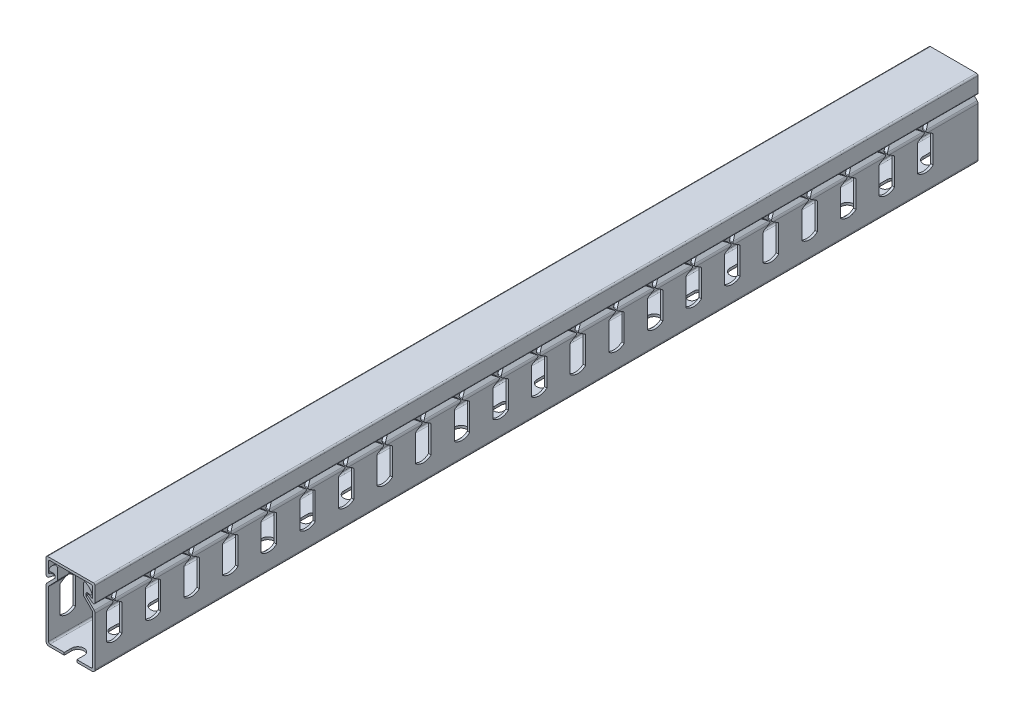
SolidWorks part; units mm, degrees
ref_plane "Front Plane" through (0, 0, 0) normal (0, 0, 1) x (1, 0, 0)
ref_plane "Top Plane" through (0, 0, 0) normal (0, 1, 0) x (1, 0, 0)
ref_plane "Right Plane" through (0, 0, 0) normal (1, 0, 0) x (0, 0, -1)
sketch "Sketch1" plane through (0, 0, 0) normal (0, 0, 1) x (1, 0, 0)
  line L0 (-12.7, 10.6985) -> (12.7, 10.6985) construction
  line L1 (12.7, -20) -> (-12.7, -20) construction
  line L2 (12.7, -20) -> (12.7, 20) construction
  line L3 (12.7, 20) -> (-12.7, 20) construction
  line L4 (-12.7, -20) -> (-12.7, 20) construction
  line L5 (0, 20) -> (0, -20) construction
  line L6 (12.7, 0) -> (-12.7, 0) construction
  line L7 (-12.7, 13.7872) -> (12.7, 13.7872) construction
  line L8 (6.8085, 20) -> (6.8085, 10.6985) construction
  line L9 (-6.8085, 20) -> (6.8085, 10.6985) construction
  line L10 (-6.8085, 20) -> (-6.8085, 10.6985) construction
  line L11 (-12.7, 18.222) -> (12.7, 18.222) construction
  line L12 (-12.7, 13.6284) -> (12.7, 13.6284) construction
  line L13 (-11.4341, 10.8542) -> (-7.685, 13.6284) construction
  line L14 (-10.1877, 13.798) -> (-6.8085, 14.3635) construction
  line L15 (12.7, 7.4) -> (6.8085, 13.4162) construction
  circle A0 centre (-11.9062, 11.4923) radius 0.7938 construction
  circle A1 centre (-10.3187, 14.5809) radius 0.7937 construction
  circle A2 centre (-7.6022, 17.4283) radius 0.7938 construction
  arc A3 (-7.9835, 18.1244) -> (-11.0321, 14.929) centre (-4.4831, 11.7329) ccw construction
  point P0 (0, 0)
  point P4 (11.43, 0)
  point P13 (0, 15.3493)
  point P16 (-11.1125, 13.7872)
  point P21 (-11.1125, 11.4923)
  point P26 (-10.3188, 13.7872)
  point P27 (-10.3188, 13.7872)
  point P28 (-11.1125, 14.5809)
  point P36 (12.7, 7.4)
  dimension "D6" = 7.2873
  dimension "Width" = 25.4
  dimension "Heigth" = 40
  dimension "Wall Thickness" = 1.27
  dimension "Cap Height" = 9.3015
  dimension "Lip Height" = 6.2128
  dimension "D1" = 13.6169
  dimension "D2" = 1.778
  dimension "Lip From Edge" = 1.5875
  dimension "D4" = 0.1588
  dimension "D5" = 36.5
  dimension "D3" = 80.5
  dimension "Shoulder Height" = 27.4
  dimension "D7" = 44.4
sketch "Sketch3" plane through (0, 0, 0) normal (1, 0, 0) x (0, 0, -1)
  line L0 (228.6, 0) -> (-228.6, 0) construction
  line L1 (-228.6, 20) -> (-228.6, -20) construction
  line L2 (-228.6, -20) -> (228.6, -20) construction
  line L3 (228.6, -20) -> (228.6, 20) construction
  line L4 (228.6, 20) -> (-228.6, 20) construction
  line L5 (-214.6, 20) -> (-214.6, 9.8437) construction
  line L6 (-214.6, 9.8437) -> (-218.473, 7.4) construction
  line L7 (-218.473, 7.4) -> (-218.727, 7.4) construction
  line L8 (-218.727, 7.4) -> (-222.6, 9.8437) construction
  line L9 (-222.6, 9.8437) -> (-222.6, 20) construction
  line L10 (-218.727, 7.4) -> (-222.6, 4.9563) construction
  line L11 (-222.6, 4.9563) -> (-222.6, -9.1796) construction
  line L12 (-222.6, -9.1796) -> (-214.6, -9.1796) construction
  line L13 (-214.6, -9.1796) -> (-214.6, 4.9563) construction
  line L14 (-218.473, 7.4) -> (-214.6, 4.9563) construction
  line L15 (-218.6, 7.4) -> (-218.6, -9.1796) construction
  line L16 (-218.6, 7.4) -> (-218.6, 20) construction
  line L17 (-222.6, 4.9563) -> (-214.6, 4.9563) construction
  line L18 (0, 7.4) -> (-218.473, 7.4) construction
  line L19 (-222.6, 9.8437) -> (-222.6, 4.9563) construction
  line L20 (-218.727, 7.4) -> (-222.6, 7.4) construction
  line L21 (-214.6, 4.9563) -> (-202.6, 4.9563) construction
  line L22 (-202.6, 4.9563) -> (-194.6, 4.9563) construction
  line L23 (-198.6, 4.9563) -> (-198.6, -9.1796) construction
  line L24 (-101.6, 20) -> (-101.6, -20) construction
  line L25 (101.6, 20) -> (101.6, -20) construction
  arc A0 (-222.6, -9.1796) -> (-214.6, -9.1796) centre (-218.6, -4.7075) ccw construction
  circle A1 centre (-219.4707, 7.4) radius 0.3969 construction
  circle A2 centre (-217.7293, 7.4) radius 0.3969 construction
  point P29 (-194.6, 4.9563)
  point P30 (-202.6, 4.9563)
  point P31 (-202.6, 4.9563)
  point P32 (-198.6, 4.9563)
  point P34 (-101.6, 0)
  point P39 (101.6, 0)
  dimension "D2" = 6
  dimension "D6" = 0.7937
  dimension "Length" = 457.2
  dimension "Side Cut Out Width" = 8
  dimension "D3" = 6
  dimension "D1" = 10.8204
  dimension "D4" = 64.5
  dimension "D5" = 0.254
  dimension "Cut Spacing" = 12
  dimension "Cut Center To Center" = 20
  dimension "D7" = 127
  dimension "D8" = 127
sketch "Sketch4" plane through (0, 0, 0) normal (0, 1, 0) x (1, 0, 0)
  line L0 (0, -232.35) -> (0, -224.85) construction
  line L1 (-12.7, 228.6) -> (12.7, 228.6) construction
  line L2 (-12.7, 228.6) -> (-12.7, -228.6) construction
  line L3 (-12.7, -228.6) -> (12.7, -228.6) construction
  line L4 (12.7, 228.6) -> (12.7, -228.6) construction
  line L5 (0, -228.6) -> (0, 228.6) construction
  line L6 (-12.7, 0) -> (12.7, 0) construction
  line L7 (-3.25, -232.35) -> (-3.25, -224.85) construction
  line L8 (3.25, -232.35) -> (3.25, -224.85) construction
  line L9 (0, -206.1) -> (0, -202.6) construction
  line L10 (-2.25, -206.1) -> (-2.25, -202.6) construction
  line L11 (2.25, -206.1) -> (2.25, -202.6) construction
  line L12 (0, -183.85) -> (0, -176.35) construction
  line L13 (-3.25, -183.85) -> (-3.25, -176.35) construction
  line L14 (3.25, -183.85) -> (3.25, -176.35) construction
  line L15 (0, -153.35) -> (0, -156.85) construction
  line L16 (2.25, -153.35) -> (2.25, -156.85) construction
  line L17 (-2.25, -153.35) -> (-2.25, -156.85) construction
  line L18 (-12.7, -101.6) -> (12.7, -101.6) construction
  line L19 (-12.7, 101.6) -> (12.7, 101.6) construction
  arc A0 (-3.25, -232.35) -> (3.25, -232.35) centre (0, -232.35) ccw construction
  arc A1 (3.25, -224.85) -> (-3.25, -224.85) centre (0, -224.85) ccw construction
  arc A2 (-2.25, -206.1) -> (2.25, -206.1) centre (0, -206.1) ccw construction
  arc A3 (2.25, -202.6) -> (-2.25, -202.6) centre (0, -202.6) ccw construction
  arc A4 (-3.25, -183.85) -> (3.25, -183.85) centre (0, -183.85) ccw construction
  arc A5 (3.25, -176.35) -> (-3.25, -176.35) centre (0, -176.35) ccw construction
  arc A6 (2.25, -153.35) -> (-2.25, -153.35) centre (0, -153.35) ccw construction
  arc A7 (-2.25, -156.85) -> (2.25, -156.85) centre (0, -156.85) ccw construction
  point P0 (0, 0)
  point P5 (0, -228.6)
  point P13 (0, -204.35)
  point P18 (0, -200.35)
  point P19 (0, -208.35)
  point P20 (0, -221.6)
  point P21 (0, -235.6)
  point P24 (0, -180.1)
  point P31 (0, -155.1)
  point P40 (0, -187.1)
  point P41 (0, -173.1)
  dimension "Large Hole Radius" = 3.25
  dimension "Large Hole Length" = 14
  dimension "Slot With" = 8
  dimension "End Hole Spacing" = 48.5
  dimension "D4" = 24.25
  dimension "Hole Spacing" = 25
  dimension "Mounting Hole Diameter" = 4.5
sketch "Sketch5" plane through (0, 0, 0) normal (0, 0, 1) x (1, 0, 0)
  line L0 (-6.8085, 17.4283) -> (-6.8085, 11.6011)
  line L1 (-6.8085, 20) -> (-6.8085, 10.6985) construction
  line L2 (-6.8085, 11.6011) -> (-11.43, 6.8817)
  line L3 (-11.43, 6.8817) -> (-11.43, -18.73)
  line L4 (-11.43, -18.73) -> (11.43, -18.73)
  line L5 (11.43, -18.73) -> (11.43, 6.8817)
  line L6 (11.43, 6.8817) -> (6.8085, 11.6011)
  line L7 (6.8085, 11.6011) -> (6.8085, 17.4283)
  line L8 (6.8085, 20) -> (6.8085, 10.6985) construction
  line L9 (12.7, 7.4) -> (6.8085, 13.4162) construction
  line L10 (0, 20) -> (0, -20) construction
  line L11 (11.43, 0) -> (12.7, 0) construction
  line L12 (8.0785, 12.1194) -> (6.8085, 12.1194) construction
  line L13 (-10.1877, 13.798) -> (-6.8085, 14.3635) construction
  line L14 (-10.1877, 13.798) -> (-8.0785, 14.151)
  line L15 (-8.0785, 14.151) -> (-8.0785, 12.1194)
  line L16 (-8.0785, 12.1194) -> (-12.7, 7.4)
  line L17 (-12.7, -20) -> (-12.7, 20) construction
  line L18 (-12.7, 7.4) -> (-12.7, -20)
  line L19 (-12.7, -20) -> (12.7, -20)
  line L20 (12.7, -20) -> (12.7, 7.4)
  line L21 (12.7, 7.4) -> (8.0785, 12.1194)
  line L22 (8.0785, 12.1194) -> (8.0785, 14.151)
  line L23 (6.8085, 12.1194) -> (-6.8085, 12.1194) construction
  line L24 (-6.8085, 12.1194) -> (-8.0785, 12.1194) construction
  line L25 (11.43, 6.8817) -> (12.3374, 7.7703) construction
  line L26 (-12.7, 18.222) -> (12.7, 18.222) construction
  line L27 (10.1877, 13.798) -> (8.0785, 14.151)
  line L28 (11.43, -18.73) -> (11.43, -20) construction
  line L29 (-12.7, 20) -> (-12.7, 11.4923)
  line L30 (-12.7, 20) -> (12.7, 20)
  line L31 (-11.4341, 10.8542) -> (-8.7512, 12.8395)
  line L32 (-11.4341, 10.8542) -> (-7.685, 13.6284) construction
  line L33 (12.7, 20) -> (12.7, 11.4923)
  line L34 (12.7, -20) -> (12.7, 20) construction
  line L35 (8.7512, 12.8395) -> (11.4341, 10.8542)
  line L36 (-12.7, 10.6985) -> (12.7, 10.6985) construction
  line L37 (-11.43, 12.4371) -> (-11.43, 18.73)
  line L38 (-11.43, 18.73) -> (11.43, 18.73)
  line L39 (11.43, 18.73) -> (11.43, 12.4371)
  line L40 (-11.43, 18.73) -> (-11.43, 20) construction
  line L41 (-11.43, 18.73) -> (-12.7, 18.73) construction
  line L42 (-11.43, 12.4371) -> (-10.6707, 12.999)
  line L43 (-11.0503, 12.7181) -> (-10.2949, 11.6972) construction
  line L44 (-8.9869, 13.5542) -> (-8.9869, 13.158) construction
  line L45 (10.6707, 12.999) -> (11.43, 12.4371)
  line L46 (10.6707, 12.999) -> (9.9153, 11.9781) construction
  circle A0 centre (-7.6022, 17.4283) radius 0.7938 construction
  arc A1 (-7.9835, 18.1244) -> (-11.0321, 14.929) centre (-4.4831, 11.7329) ccw construction
  arc A2 (-7.9835, 18.1244) -> (-11.0321, 14.929) centre (-4.4831, 11.7329) ccw
  circle A3 centre (-10.3187, 14.5809) radius 0.7937 construction
  arc A4 (-11.0321, 14.929) -> (-10.1877, 13.798) centre (-10.3187, 14.5809) ccw
  arc A5 (-6.8085, 17.4283) -> (-7.9835, 18.1244) centre (-7.6022, 17.4283) ccw
  arc A6 (7.9835, 18.1244) -> (6.8085, 17.4283) centre (7.6022, 17.4282) ccw
  arc A7 (10.1877, 13.798) -> (11.0321, 14.929) centre (10.3187, 14.5809) ccw
  arc A8 (7.9835, 18.1244) -> (11.0321, 14.929) centre (4.4831, 11.7329) cw
  circle A9 centre (-11.9062, 11.4923) radius 0.7938 construction
  arc A10 (-12.7, 11.4923) -> (-11.4341, 10.8542) centre (-11.9062, 11.4923) ccw
  arc A11 (11.4341, 10.8542) -> (12.7, 11.4923) centre (11.9062, 11.4923) ccw
  arc A12 (-8.7512, 12.8395) -> (-8.9869, 13.5542) centre (-8.9869, 13.158) ccw
  arc A13 (-10.6707, 12.999) -> (-8.9869, 13.5542) centre (-8.9869, 10.7234) cw
  arc A14 (8.7512, 12.8395) -> (8.9869, 13.5542) centre (8.9869, 13.158) cw
  arc A15 (8.9869, 13.5542) -> (10.6707, 12.999) centre (8.9869, 10.7234) cw
  point P10 (0, -18.73)
  point P81 (0, 18.73)
  dimension "D2" = 0.3962
  dimension "D1" = 3.3376
extrude "Boss-Extrude1" add sketch "Sketch5" along normal up to vertex (228.6 mm away) and the other way up to vertex (228.6 mm away) up to point (0, -20, 228.6) other way up to point (0, -20, -228.6)
fillet "Fillet1" radius 0.254 2 edges at (-11.43, 12.4371, 0) (11.43, 12.4371, 0)
fillet "Fillet2" radius 0.7937 4 edges at (12.7, 20, 0) (11.43, 18.73, 0) (-11.43, 18.73, 0) (-12.7, 20, 0)
fillet "Fillet3" radius 1.5875 4 edges at (-12.7, -20, 0) (12.7, -20, 0) (12.7, 7.4, 0) (-12.7, 7.4, 0)
fillet "Fillet4" radius 0.7937 8 edges at (-11.43, -18.73, 0) (11.43, -18.73, 0) (8.0785, 14.151, 0) (-8.0785, 14.151, 0) (-11.43, 6.8817, 0) (-6.8085, 11.6011, 0) (6.8085, 11.6011, 0) (11.43, 6.8817, 0)
sketch "Sketch6" plane through (0, 0, 0) normal (1, 0, 0) x (0, 0, -1)
  line L0 (-222.6, 20) -> (-222.6, 10.2814)
  line L1 (-222.6, 4.9563) -> (-222.6, -9.1796) construction
  line L2 (-218.727, 7.4) -> (-222.6, 4.9563) construction
  line L3 (-214.6, -9.1796) -> (-214.6, 4.9563) construction
  line L4 (-218.473, 7.4) -> (-214.6, 4.9563) construction
  line L5 (-214.6, 9.8437) -> (-218.473, 7.4) construction
  line L6 (-214.6, 20) -> (-214.6, 9.8437) construction
  line L7 (-218.727, 7.4) -> (-222.6, 9.8437) construction
  line L8 (-222.6, 4.5186) -> (-222.6, -9.1796)
  line L9 (-219.259, 7.0644) -> (-222.2298, 5.1899)
  line L10 (-214.6, -9.1796) -> (-214.6, 4.5186)
  line L11 (-217.941, 7.0644) -> (-214.9702, 5.1899)
  line L12 (-214.9702, 9.6101) -> (-217.941, 7.7356)
  line L13 (-214.6, 20) -> (-214.6, 10.2814)
  line L14 (-219.259, 7.7356) -> (-222.2298, 9.6101)
  line L15 (-214.6, 20) -> (-222.6, 20)
  circle A0 centre (-217.7293, 7.4) radius 0.3969 construction
  circle A1 centre (-219.4707, 7.4) radius 0.3969 construction
  arc A2 (-217.941, 7.7356) -> (-217.941, 7.0644) centre (-217.7293, 7.4) ccw
  arc A3 (-219.259, 7.0644) -> (-219.259, 7.7356) centre (-219.4707, 7.4) ccw
  arc A4 (-222.6, -9.1796) -> (-214.6, -9.1796) centre (-218.6, -4.7075) ccw construction
  arc A5 (-222.6, -9.1796) -> (-214.6, -9.1796) centre (-218.6, -4.7075) ccw
  arc A6 (-214.9702, 9.6101) -> (-214.6, 10.2814) centre (-215.3937, 10.2814) ccw
  arc A7 (-214.6, 4.5186) -> (-214.9702, 5.1899) centre (-215.3937, 4.5186) ccw
  arc A8 (-222.6, 4.5186) -> (-222.2298, 5.1899) centre (-221.8062, 4.5186) cw
  arc A9 (-222.6, 10.2814) -> (-222.2298, 9.6101) centre (-221.8062, 10.2814) ccw
  dimension "D1" = 0.7937
extrude "Cut-Extrude2" cut sketch "Sketch6" against normal through all both and the other way through all
pattern_linear "LPattern2" count 22 spacing 20 along (0, 0, -1) of "Cut-Extrude2"
sketch "Sketch7" plane through (0, -20, 0) normal (0, -1, 0) x (1, 0, 0)
  line L0 (-3.25, 232.35) -> (-3.25, 224.85) construction
  line L1 (3.25, 232.35) -> (3.25, 224.85) construction
  line L2 (-3.25, 232.35) -> (-3.25, 224.85)
  line L3 (3.25, 232.35) -> (3.25, 224.85)
  line L4 (-2.25, 206.1) -> (-2.25, 202.6) construction
  line L5 (2.25, 206.1) -> (2.25, 202.6) construction
  line L6 (-2.25, 206.1) -> (-2.25, 202.6)
  line L7 (2.25, 206.1) -> (2.25, 202.6)
  arc A0 (3.25, 232.35) -> (-3.25, 232.35) centre (0, 232.35) ccw construction
  arc A1 (-3.25, 224.85) -> (3.25, 224.85) centre (0, 224.85) ccw construction
  arc A2 (3.25, 232.35) -> (-3.25, 232.35) centre (0, 232.35) ccw
  arc A3 (-3.25, 224.85) -> (3.25, 224.85) centre (0, 224.85) ccw
  arc A4 (2.25, 206.1) -> (-2.25, 206.1) centre (0, 206.1) ccw construction
  arc A5 (-2.25, 202.6) -> (2.25, 202.6) centre (0, 202.6) ccw construction
  arc A6 (2.25, 206.1) -> (-2.25, 206.1) centre (0, 206.1) ccw
  arc A7 (-2.25, 202.6) -> (2.25, 202.6) centre (0, 202.6) ccw
extrude "Cut-Extrude3" cut sketch "Sketch7" against normal up to vertex (1.27 mm away) up to point (10.6363, -18.73, 228.6)
sketch "Sketch8" plane through (0, -20, 0) normal (0, -1, 0) x (1, 0, 0)
  line L0 (-2.25, 153.35) -> (-2.25, 156.85) construction
  line L1 (2.25, 153.35) -> (2.25, 156.85) construction
  line L2 (3.25, 183.85) -> (3.25, 176.35) construction
  line L3 (-3.25, 183.85) -> (-3.25, 176.35) construction
  line L4 (-2.25, 153.35) -> (-2.25, 156.85)
  line L5 (2.25, 153.35) -> (2.25, 156.85)
  line L6 (3.25, 183.85) -> (3.25, 176.35)
  line L7 (-3.25, 183.85) -> (-3.25, 176.35)
  arc A0 (-2.25, 153.35) -> (2.25, 153.35) centre (0, 153.35) ccw construction
  arc A1 (2.25, 156.85) -> (-2.25, 156.85) centre (0, 156.85) ccw construction
  arc A2 (3.25, 183.85) -> (-3.25, 183.85) centre (0, 183.85) ccw construction
  arc A3 (-3.25, 176.35) -> (3.25, 176.35) centre (0, 176.35) ccw construction
  arc A4 (-2.25, 153.35) -> (2.25, 153.35) centre (0, 153.35) ccw
  arc A5 (2.25, 156.85) -> (-2.25, 156.85) centre (0, 156.85) ccw
  arc A6 (3.25, 183.85) -> (-3.25, 183.85) centre (0, 183.85) ccw
  arc A7 (-3.25, 176.35) -> (3.25, 176.35) centre (0, 176.35) ccw
extrude "Cut-Extrude4" cut sketch "Sketch8" against normal up to vertex (1.27 mm away) up to point (-3.25, -18.73, 228.6)
pattern_linear "LPattern3" count 10 spacing 50 along (0, 0, -1) of "Cut-Extrude4"
equation "\"D2@Sketch1\"=\"Wall Thickness@Sketch1\"*1.4"
equation "\"D4@Sketch1\"=\"Wall Thickness@Sketch1\"*.125"
equation "\"D2@Sketch3\" = \"Side Cut Out Width@Sketch3\" * .75"
equation "\"D4@Sketch4\" = \"End Hole Spacing@Sketch4\" / 2"
equation "\"D3@LPattern2\"=\"Cut Center To Center@Sketch3\""
equation "\"D1@LPattern2\"=\"Length@Sketch3\"/\"Cut Center To Center@Sketch3\"-1"
equation "\"D1@LPattern3\"=(\"Length@Sketch3\"/50mm)+1"
equation "\"D7@Sketch3\"=\"D8@Sketch3\""
